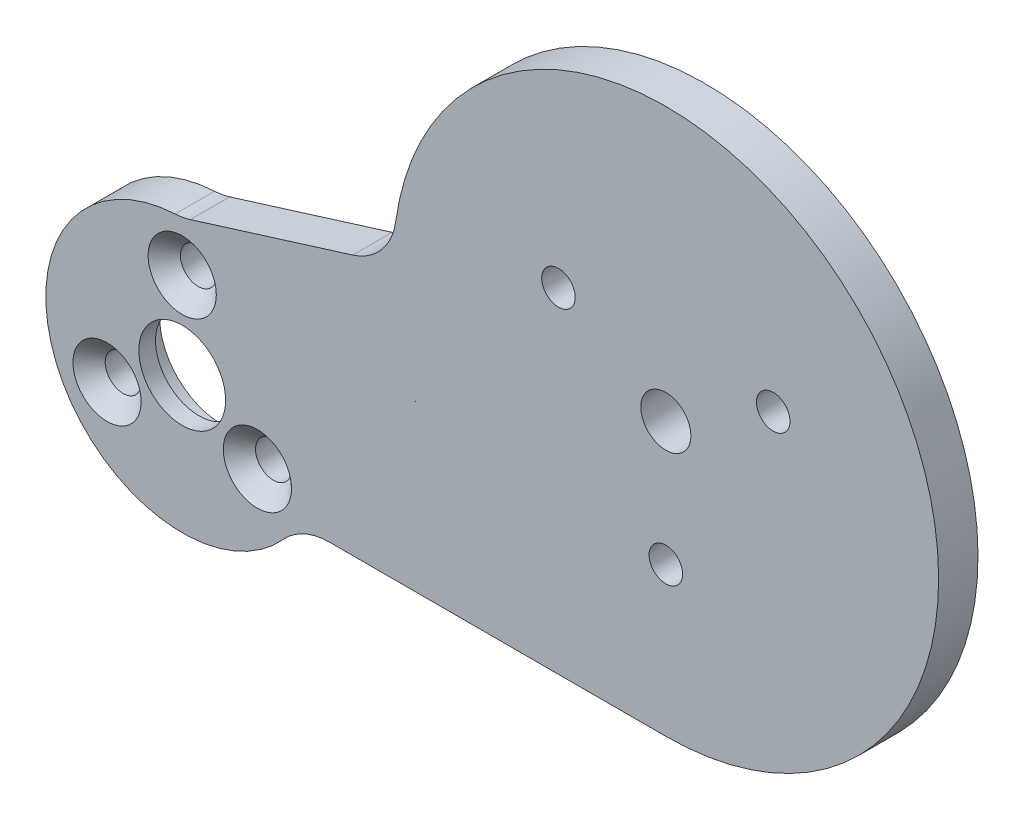
SolidWorks part; units mm, degrees
material "6061 Alloy"
ref_plane "Front Plane" through (0, 0, 0) normal (0, 0, 1) x (1, 0, 0)
ref_plane "Top Plane" through (0, 0, 0) normal (0, 1, 0) x (1, 0, 0)
ref_plane "Right Plane" through (0, 0, 0) normal (1, 0, 0) x (0, 0, -1)
sketch "Sketch1" plane through (0, 0, 0) normal (0, 0, 1) x (1, 0, 0)
  line L0 (-22, 0) -> (-52, 0)
  line L1 (-52, 0) -> (-52, -35)
  line L2 (-52, -35) -> (-22, -35)
  line L3 (0, 0) -> (0, -11.828) construction
  line L4 (0, -11.828) -> (-18.5499, -11.828) construction
  line L5 (-22, -35) -> (-20.1587, -8.8105)
  line L6 (-39, 0) -> (-39, -35) construction
  line L7 (-52, -16.2877) -> (-39, -16.2877) construction
  line L8 (-52, -16.2877) -> (-52, -35)
  line L9 (0, -22) -> (-19.5573, -22)
  line L10 (-39, -5.2877) -> (-22, 0)
  line L11 (-19.5573, -22) -> (-29.5995, -22)
  circle A0 centre (0, 0) radius 22
  circle A1 centre (-39, -16.2877) radius 3.5001
  circle A2 centre (-39, -16.2877) radius 5
  circle A3 centre (-39, -16.2877) radius 20.2645
  circle A4 centre (-39, -16.2877) radius 11
  dimension "D1" = 17
  dimension "D2" = 16.2877
extrude "Body" add sketch "Sketch1" along normal blind 3.175 contours A0 | A3 L9 A0 L5 | L11 A3 L5 | A3 A0 L10 | A4 L11 L5 A3 L10 | A4 A2 | A2 A1 region at (-22.8892, -2.5054, 0) region at (0, 0, 0) region at (-26.1096, -11.0295, 0) region at (-31.4418, -8.7295, 0) region at (-14.5385, -18.9157, 0) region at (-19.849, -16.518, 0) region at (-43.8586, -16.2877, 0)
hole_wizard "CSK for M2.5 Flat Head Machine Screw1" positions "3DSketch1" profile "Sketch2" countersink size "M2.5" standard "Ansi Metric" end condition through all
sketch3d "3DSketch1"
  line L0 (-39, -16.2877, 3.175) -> (-39, 0, 3.175) construction
  line L3 (-39, -16.2877, 3.175) -> (-28.4318, -22.3892, 3.175) construction
  line L4 (-39, -16.2877, 3.175) -> (-49.9954, -22.6359, 3.175) construction
  circle A0 centre (-39, -16.2877, 3.175) radius 7
  circle A2 centre (-39, -16.2877, 3.175) radius 3.5001 construction
  point P0 (-39, -9.2877, 3.175)
  point P2 (-45.0622, -19.7877, 3.175)
  point P4 (-32.9378, -19.7877, 3.175)
  point P16 (-39, -16.2877, 10.175)
  point P28 (-39, -16.2877, 6.6751)
  dimension "D1" = 120
  dimension "D3" = 14
  dimension "D2" = 120
sketch "Sketch2" plane through (-39, -9.2877, 3.175) normal (1, 0, 0) x (0, -1, 0)
  line L0 (0, 0) -> (0, 3.175)
  line L1 (0, 3.175) -> (1.45, 3.175)
  line L2 (1.45, 3.175) -> (1.45, 1.3)
  line L3 (1.45, 1.3) -> (2.75, 0)
  line L5 (2.75, 0) -> (0, 0)
  line L6 (-1.45, 1.3) -> (-2.75, 0) construction
  line L11 (0, -6.35) -> (0, 107.95) construction
  dimension "Thru Hole Dia." = 2.9
  dimension "Thru Hole Depth" = 3.175
  dimension "Near C'Sink Dia." = 5.5
  dimension "Near C'Sink Angle" = 90
fillet "Fillet1" radius 5 3 edges at (-29.5995, -22, 1.5875) (-39, -5.2877, 1.5875) (-22, 0, 1.5875)
hole_wizard "#10-32 Tapped Hole2" positions "3DSketch4" profile "Sketch5" tap size "#10-32" standard "Ansi Inch"
sketch3d "3DSketch4"
  line L2 (0, 10, 3.175) -> (-8.6603, -5, 3.175) construction
  line L7 (8.6603, -5, 3.175) -> (-8.6603, -5, 3.175) construction
  line L9 (8.6603, -5, 3.175) -> (0, 10, 3.175) construction
  line L10 (-8.6603, -5, 3.175) -> (4.3301, 2.5, 3.175) construction
  line L11 (8.6603, -5, 3.175) -> (-4.3301, 2.5, 3.175) construction
  point P0 (0, 0, 3.175)
sketch "Sketch5" plane through (0, 0, 3.175) normal (1, 0, 0) x (0, -1, 0)
  line L0 (0, 0) -> (0, 13.2433)
  line L1 (0, 13.2433) -> (2.0193, 12.03)
  line L2 (2.0193, 12.03) -> (2.0193, 0)
  line L5 (2.0193, 0) -> (0, 0)
  line L10 (0, 13.2433) -> (-2.0193, 12.03) construction
  line L11 (0, -6.35) -> (0, 107.95) construction
  dimension "Tap Drill Dia." = 4.0386
  dimension "Tap Drill Depth" = 12.03
  dimension "Drill Angle" = 118
cosmetic thread "Hole Thread6" parameters "D1"=3.175, "D2"=4.826
hole_wizard "#6-32 Tapped Hole1" positions "3DSketch5" profile "Sketch6" tap size "#6-32" standard "Ansi Inch"
sketch3d "3DSketch5"
  line L1 (0, 0, 0) -> (0, -22, 0) construction
  line L2 (0, 0, 0) -> (-19.0526, 11, 0) construction
  line L3 (0, 0, 0) -> (19.0526, 11, 0) construction
  line L4 (0, 0, 0) -> (0, 0, -28.5987) construction
  circle A0 centre (0, 0, 0) radius 22
  circle A1 centre (0, 0, 0) radius 10
  arc A2 (0, -22, 0) -> (-21.7853, 3.0662, 0) centre (0, 0, 0) ccw construction
  point P0 (-8.6603, 5, 0)
  point P2 (8.6603, 5, 0)
  point P4 (0, -10, 0)
  point P9 (0, 0, 22)
  point P15 (0, 0, 10)
  point P37 (0, 0, 22)
  dimension "D1" = 120
  dimension "D3" = 20
  dimension "D2" = 120
sketch "Sketch6" plane through (-8.6603, 5, 0) normal (1, 0, 0) x (0, 1, 0)
  line L0 (0, 0) -> (0, 10.2027)
  line L1 (0, 10.2027) -> (1.3525, 9.39)
  line L2 (1.3525, 9.39) -> (1.3525, 0)
  line L5 (1.3525, 0) -> (0, 0)
  line L10 (0, 10.2027) -> (-1.3525, 9.39) construction
  line L11 (0, -6.35) -> (0, 107.95) construction
  dimension "Tap Drill Dia." = 2.7051
  dimension "Tap Drill Depth" = 9.39
  dimension "Drill Angle" = 118
cosmetic thread "Hole Thread10" parameters "D1"=3.175, "D2"=3.5052
cosmetic thread "Hole Thread11" parameters "D1"=3.175, "D2"=3.5052
cosmetic thread "Hole Thread12" parameters "D1"=3.175, "D2"=3.5052
extrude "Motor Collar Recess" cut sketch "Sketch1<3>" along normal blind 1.8263 contours A2 A1 region at (-43.8586, -16.2877, 0)
sketch "Sketch1<3>" plane through (0, 0, 0) normal (0, 0, 1) x (1, 0, 0) same geometry as "Sketch1"
